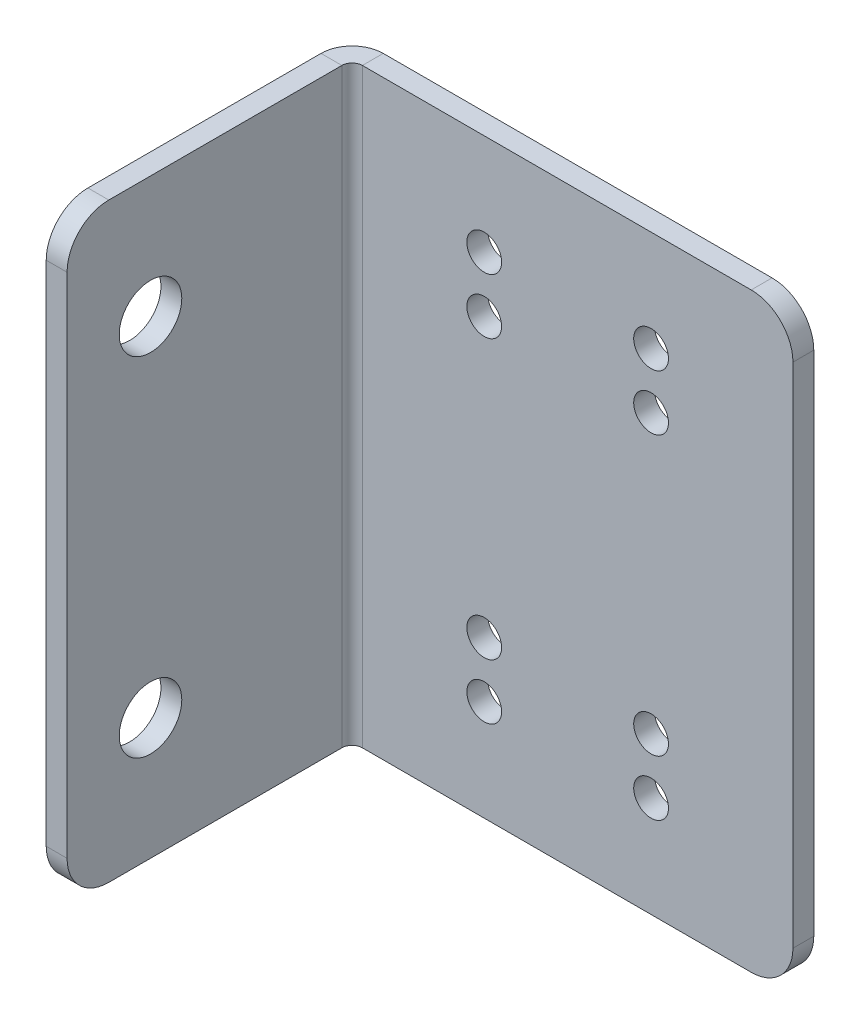
SolidWorks part; units mm, degrees
note: The reader was unsure of these and kept them because the rebuilt part matched: flange length of "边线-法兰1".
ref_plane "前视基准面" through (0, 0, 0) normal (0, 0, 1) x (1, 0, 0)
ref_plane "上视基准面" through (0, 0, 0) normal (0, 1, 0) x (1, 0, 0)
ref_plane "右视基准面" through (0, 0, 0) normal (1, 0, 0) x (0, 0, -1)
sketch "草图1" plane through (0, 0, 0) normal (0, 0, 1) x (1, 0, 0)
  line L1 (16.6, -21.25) -> (-16.6, -21.25)
  line L2 (16.6, -21.25) -> (16.6, 21.25)
  line L3 (16.6, 21.25) -> (-16.6, 21.25)
  line L4 (-16.6, -21.25) -> (-16.6, 21.25)
  line L5 (16.6, -21.25) -> (-16.6, 21.25) construction
  line L6 (16.6, 21.25) -> (-16.6, -21.25) construction
  point P0 (0, 0)
  dimension "D1" = 42.5
  dimension "D2" = 33.2
base flange "基体-法兰1" sketch "草图1" thickness 1.5 reverse thickness direction no parameters "D1"=0.7366
edge flange "边线-法兰1" sketch "草图8" flange angle 90 flange length 22 flange position material inside bend radius 0.7366 thickness 1.5 relief rectangular parameters "D6"=10
sketch "草图8" plane through (-16.6, 0, 0) normal (-1, 0, 0) x (0, -1, 0)
  line L2 (-21.25, 0) -> (-21.25, 20.5)
  line L3 (-21.25, 20.5) -> (21.25, 20.5)
  line L4 (21.25, 20.5) -> (21.25, 0)
  line L7 (-21.25, 0) -> (21.25, 0) construction
  line L8 (-21.25, 0) -> (21.25, 0)
bend "边线折弯1" bend radius 0.7366 bend angle 90 parameters "D5"=1
sketch "草图9" plane through (0, 0, 0) normal (0, 0, 1) x (1, 0, 0)
  circle A0 centre (6.4, 14) radius 1.25
  circle A1 centre (-5.6, 14) radius 1.25
  circle A2 centre (6.4, -10) radius 1.25
  circle A3 centre (-5.6, -10) radius 1.25
  dimension "D1" = 2.5
extrude "切除-拉伸1" cut sketch "草图9" against normal blind 10
sketch "草图10" plane through (-15.1, 0, 0) normal (1, 0, 0) x (0, 0, -1)
  line L0 (0, 0) -> (-20.5, 0) construction
  line L1 (-20.5, -21.25) -> (-20.5, 21.25) construction
  circle A0 centre (-14.5, 12.5) radius 2.25
  circle A1 centre (-14.5, -12.5) radius 2.25
  dimension "D2" = 6
  dimension "D3" = 4.5
  dimension "D1" = 25
extrude "切除-拉伸2" cut sketch "草图10" against normal blind 10
mirror "镜向1" about plane through (0, 0, 0) normal (0, 1, 0) of "切除-拉伸1"
fillet "圆角1" radius 3 4 edges at (-15.85, -21.25, 20.5) (16.6, -21.25, -0.75) (16.6, 21.25, -0.75) (-15.85, 21.25, 20.5)
sketch "折弯-线1" plane through (0, 0, 0) normal (0, 1, 0) x (1, 0, 0)
sketch "边界框1" plane through (0, 0, 0) normal (0, 1, 0) x (1, 0, 0)
sheet metal parameters "钣金6" thickness 1.5 parameters "D1"=0.7366
flat pattern "平板型式6" [suppressed]
sketch "折弯-线2" plane through (0, 0, 0) normal (0, 1, 0) x (1, 0, 0)
sketch "边界框2" [suppressed] plane through (0, 0, 0) normal (0, 1, 0) x (1, 0, 0)
sheet metal parameters "钣金7" thickness 1.5 parameters "D1"=0.7366
flat pattern "平板型式6" [suppressed]
sketch "折弯-线2" plane through (0, 0, 0) normal (0, 1, 0) x (1, 0, 0)
sketch "边界框2" [suppressed] plane through (0, 0, 0) normal (0, 1, 0) x (1, 0, 0)
bend of the flat pattern "展平-<边线折弯1>1"
sheet metal parameters "钣金8" thickness 1.5 parameters "D1"=0.7366
flat pattern "平板型式6" [suppressed]
sketch "折弯-线2" plane through (0, 0, 0) normal (0, 1, 0) x (1, 0, 0)
sketch "边界框2" [suppressed] plane through (0, 0, 0) normal (0, 1, 0) x (1, 0, 0)
bend of the flat pattern "展平-<边线折弯1>1"
sheet metal parameters "钣金9" thickness 1.5 parameters "D1"=0.7366
flat pattern "平板型式6" [suppressed]
sketch "折弯-线2" plane through (0, 0, 0) normal (0, 1, 0) x (1, 0, 0)
sketch "边界框2" [suppressed] plane through (0, 0, 0) normal (0, 1, 0) x (1, 0, 0)
bend of the flat pattern "展平-<边线折弯1>1"
sheet metal parameters "钣金10" thickness 1.5 parameters "D1"=0.7366
flat pattern "平板型式6" [suppressed]
sketch "折弯-线2" plane through (0, 0, 0) normal (0, 1, 0) x (1, 0, 0)
sketch "边界框2" [suppressed] plane through (0, 0, 0) normal (0, 1, 0) x (1, 0, 0)
bend of the flat pattern "展平-<边线折弯1>1"
